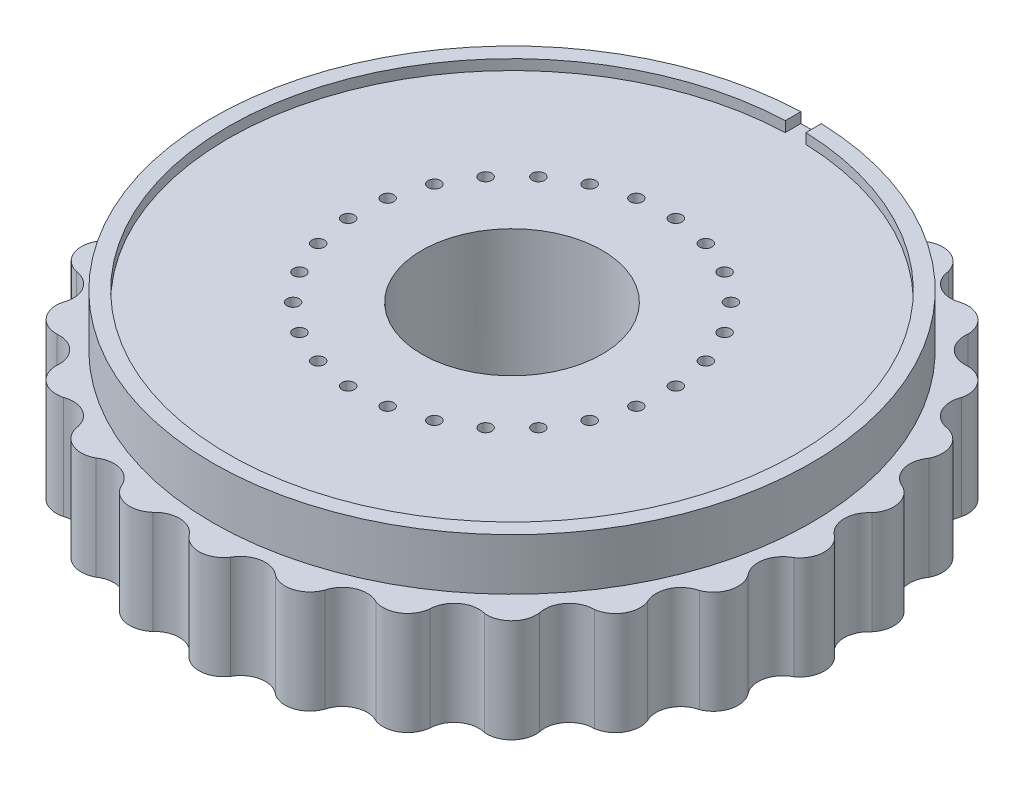
SolidWorks part; units mm, degrees
ref_plane "Front Plane" through (0, 0, 0) normal (0, 0, 1) x (1, 0, 0)
ref_plane "Top Plane" through (0, 0, 0) normal (0, 1, 0) x (1, 0, 0)
ref_plane "Right Plane" through (0, 0, 0) normal (1, 0, 0) x (0, 0, -1)
sketch "Wheel" plane through (0, 0, 0) normal (0, 1, 0) x (1, 0, 0)
  line L0 (0, 0) -> (45.5848, 0) construction
  line L1 (0, 0) -> (41.8043, 10.3038) construction
  line L2 (0, 0) -> (29.1283, 7.1795)
  line L3 (0, 0) -> (30, 0)
  line L4 (0, 0) -> (42.9769, 5.2183) construction
  line L5 (29.1283, 7.1795) -> (30.3419, 7.4786)
  line L6 (30, 0) -> (31.25, 0)
  circle A0 centre (0, 0) radius 30 construction
  circle A1 centre (0, 0) radius 32.5 construction
  circle A2 centre (0, 0) radius 31.25 construction
  arc A3 (30.3419, 7.4786) -> (31.0877, 3.7747) centre (29.2636, 5.3345) cw
  arc A4 (31.0877, 3.7747) -> (31.25, 0) centre (0.4989, 0.5684) ccw construction
  arc A5 (31.0877, 3.7747) -> (31.25, 0) centre (32.6478, 1.951) ccw
  circle A6 centre (32.6478, 1.951) radius 2.4 construction
  dimension "D1" = 60
  dimension "D2" = 2.5
  dimension "D4" = 1.25
  dimension "D5" = 6.923
  dimension "D6" = 4.8
  dimension "D3" = 13.846
extrude "Extrude wheel" add sketch "Wheel" along normal blind 10
pattern_circular "CirPattern1" count 26 over 360 about axis through (0, 10, 0) along (0, -1, 0) of "Extrude wheel" reverse direction yes
sketch "Sketch4" plane through (0, 10, 0) normal (0, 1, 0) x (1, 0, 0)
  circle A0 centre (0, 0) radius 29
  dimension "D1" = 58
extrude "Boss-Extrude1" add sketch "Sketch4" along normal blind 5
sketch "Bearing hole" plane through (0, 15, 0) normal (0, 1, 0) x (1, 0, 0)
  circle A0 centre (0, 0) radius 8.7313
  dimension "D1" = 17.4625
extrude "Cut bearing hole" cut sketch "Bearing hole" against normal through all
sketch "PCB inset" plane through (0, 15, 0) normal (0, 1, 0) x (1, 0, 0)
  line L0 (-1, 27.4818) -> (-1, 29.4818)
  line L1 (-1, 29.4818) -> (1, 29.4818)
  line L2 (1, 29.4818) -> (1, 27.4818)
  line L3 (0, 0) -> (0, 37.4364) construction
  arc A0 (-1, 27.4818) -> (1, 27.4818) centre (0, 0) ccw
  point P7 (0, 29.4818)
  dimension "D1" = 55
  dimension "D3" = 2
  dimension "D2" = 2
extrude "PCB inset cut" cut sketch "PCB inset" against normal blind 1
sketch "PCB inset 2" plane through (0, 0, 0) normal (0, -1, 0) x (1, 0, 0)
  line L0 (0, 0) -> (0, -38.2083) construction
  line L1 (1, -27.4818) -> (1, -29.4818)
  line L2 (1, -29.4818) -> (-1, -29.4818)
  line L3 (-1, -29.4818) -> (-1, -27.4818)
  arc A0 (1, -27.4818) -> (-1, -27.4818) centre (0, 0) ccw
  point P8 (0, -29.4818)
  dimension "D1" = 55
  dimension "D2" = 2
  dimension "D3" = 2
extrude "PCB inset cut 2" cut sketch "PCB inset 2" against normal blind 1
sketch "PCB output holes" plane through (0, 14, 0) normal (0, 1, 0) x (1, 0, 0)
  line L0 (0, 0) -> (60.8892, 0) construction
  line L1 (0, 0) -> (59.1575, 14.581) construction
  line L2 (0, 0) -> (60.7873, 3.677) construction
  circle A0 centre (14.9726, 0.9057) radius 0.6
  circle A1 centre (14.7543, -2.7038) radius 0.6
  circle A2 centre (13.6785, -6.1562) radius 0.6
  circle A3 centre (11.8078, -9.2508) radius 0.6
  circle A4 centre (9.2508, -11.8078) radius 0.6
  circle A5 centre (6.1562, -13.6785) radius 0.6
  circle A6 centre (2.7038, -14.7543) radius 0.6
  circle A7 centre (-0.9057, -14.9726) radius 0.6
  circle A8 centre (-4.4625, -14.3208) radius 0.6
  circle A9 centre (-7.7601, -12.8367) radius 0.6
  circle A10 centre (-10.6066, -10.6066) radius 0.6
  circle A11 centre (-12.8367, -7.7601) radius 0.6
  circle A12 centre (-14.3208, -4.4625) radius 0.6
  circle A13 centre (-14.9726, -0.9057) radius 0.6
  circle A14 centre (-14.7543, 2.7038) radius 0.6
  circle A15 centre (-13.6785, 6.1562) radius 0.6
  circle A16 centre (-11.8078, 9.2508) radius 0.6
  circle A17 centre (-9.2508, 11.8078) radius 0.6
  circle A18 centre (-6.1562, 13.6785) radius 0.6
  circle A19 centre (-2.7038, 14.7543) radius 0.6
  circle A20 centre (0.9057, 14.9726) radius 0.6
  circle A21 centre (4.4625, 14.3208) radius 0.6
  circle A22 centre (7.7601, 12.8367) radius 0.6
  circle A23 centre (10.6066, 10.6066) radius 0.6
  circle A24 centre (12.8367, 7.7601) radius 0.6
  circle A25 centre (14.3208, 4.4625) radius 0.6
  point P60 (0, 0)
  dimension "D5" = 1.2
  dimension "D1" = 13.846
  dimension "D2" = 3.462
  dimension "D3" = 15
  dimension "D4" = 26
extrude "PCB output holes cut" cut sketch "PCB output holes" against normal through all
equation "\"Diameter\"=60"
equation "\"D1@Wheel\"=\"Diameter\""
equation "\"D5@Wheel\"=360/26/2"
equation "\"Bearing size\"= 17.4625mm"
equation "\"D1@Bearing hole\"=\"Bearing size\""
equation "\"PCB diameter\"= 55mm"
equation "\"D1@PCB inset\"=\"PCB diameter\""
equation "\"D1@PCB inset 2\"=\"PCB diameter\""
equation "\"D2@PCB output holes\"=360/26/4"
